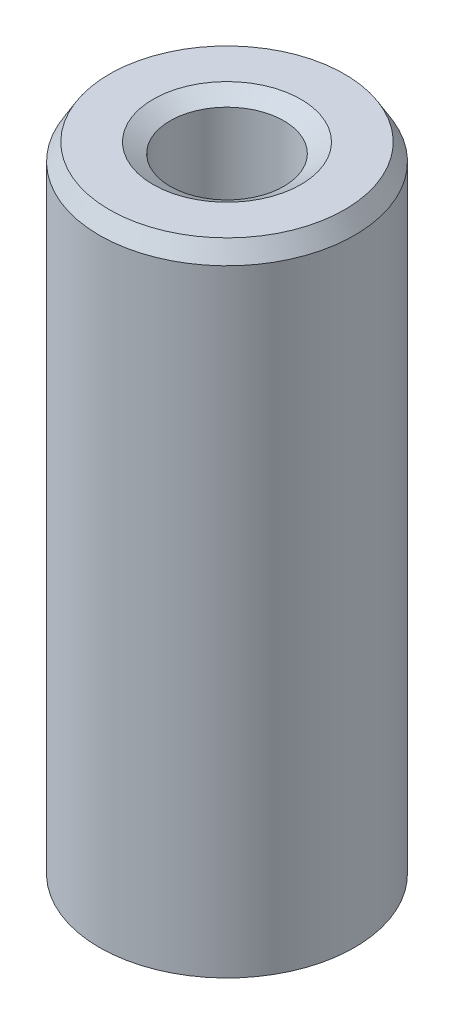
SolidWorks part; units mm, degrees
ref_plane "Front Plane" through (0, 0, 0) normal (0, 0, 1) x (1, 0, 0)
ref_plane "Top Plane" through (0, 0, 0) normal (0, 1, 0) x (1, 0, 0)
ref_plane "Right Plane" through (0, 0, 0) normal (1, 0, 0) x (0, 0, -1)
sketch "Sketch1" plane through (0, 0, 0) normal (0, 1, 0) x (1, 0, 0)
  circle A0 centre (0, 0) radius 7.5
  dimension "SLEEVE_OD" = 15
extrude "Boss-Extrude1" add sketch "Sketch1" along normal blind 37.8421
sketch "Sketch2" plane through (0, 0, 0) normal (0, 1, 0) x (1, 0, 0)
  circle A0 centre (0, 0) radius 3.3405
  dimension "BORE_D" = 6.681
extrude "Cut-Extrude1" cut sketch "Sketch2" along normal through all
chamfer "Chamfer1" distance 1.0033 angle 30.553 4 edges at (0, 37.8421, 3.3405) (0, 0, 3.3405) (0, 0, 7.5) (0, 37.8421, 7.5) first distance on face at (0, 37.8421, 3.3405) first distance on face at (0, 0, 3.3405) first distance on face at (0, 37.8421, 7.5)
